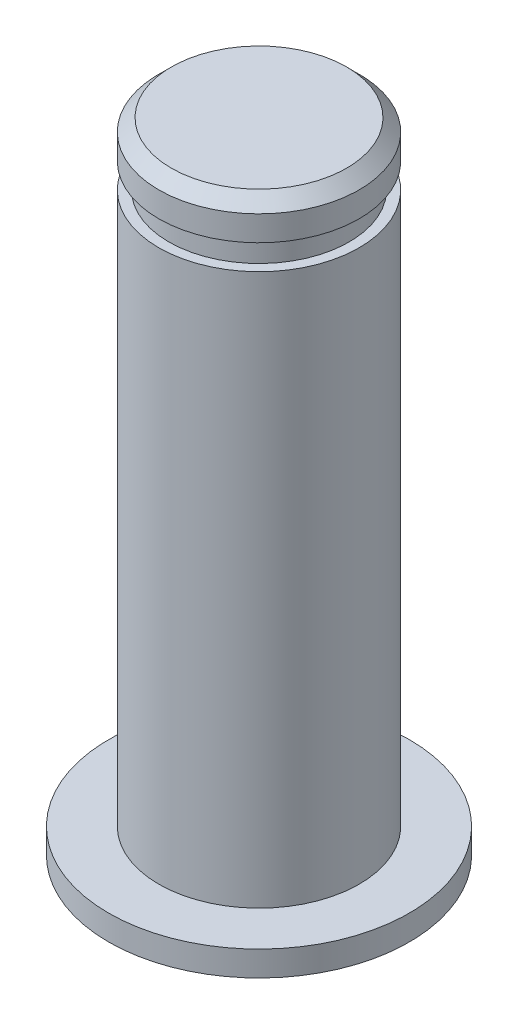
SolidWorks part; units mm, degrees
ref_plane "Спереди" through (0, 0, 0) normal (0, 0, 1) x (1, 0, 0)
ref_plane "Сверху" through (0, 0, 0) normal (0, 1, 0) x (1, 0, 0)
ref_plane "Справа" through (0, 0, 0) normal (1, 0, 0) x (0, 0, -1)
sketch "Эскиз1" plane through (0, 0, 0) normal (0, 0, 1) x (1, 0, 0)
  line L0 (-4, 25.5) -> (0, 25.5)
  line L1 (0, 25.5) -> (0, 0)
  line L2 (0, 0) -> (-6, 0)
  line L3 (-6, 0) -> (-6, 1)
  line L4 (-6, 1) -> (-4, 1)
  line L5 (-4, 1) -> (-4, 23)
  line L6 (-4, 23) -> (-3.6, 23)
  line L7 (-3.6, 23) -> (-3.6, 24)
  line L8 (-3.6, 24) -> (-4, 24)
  line L9 (-4, 24) -> (-4, 25.5)
  line L10 (0, 0) -> (0, -50000) construction
  line L12 (4, 23) -> (-4, 23) construction
  line L13 (4, 23) -> (-4, 23) construction
  line L14 (4, 23) -> (-4, 23) construction
  line L16 (3.6, 24) -> (-3.6, 24) construction
  line L18 (3.6, 24) -> (-3.6, 24) construction
  dimension "D1" = 1.5
  dimension "D2" = 2
  dimension "D3" = 1
revolve "Повернуть1" add sketch "Эскиз1" angle 360 about L10
chamfer "Фаска1" distance 0.5 angle 45 1 edges at (0, 25.5, 4)
